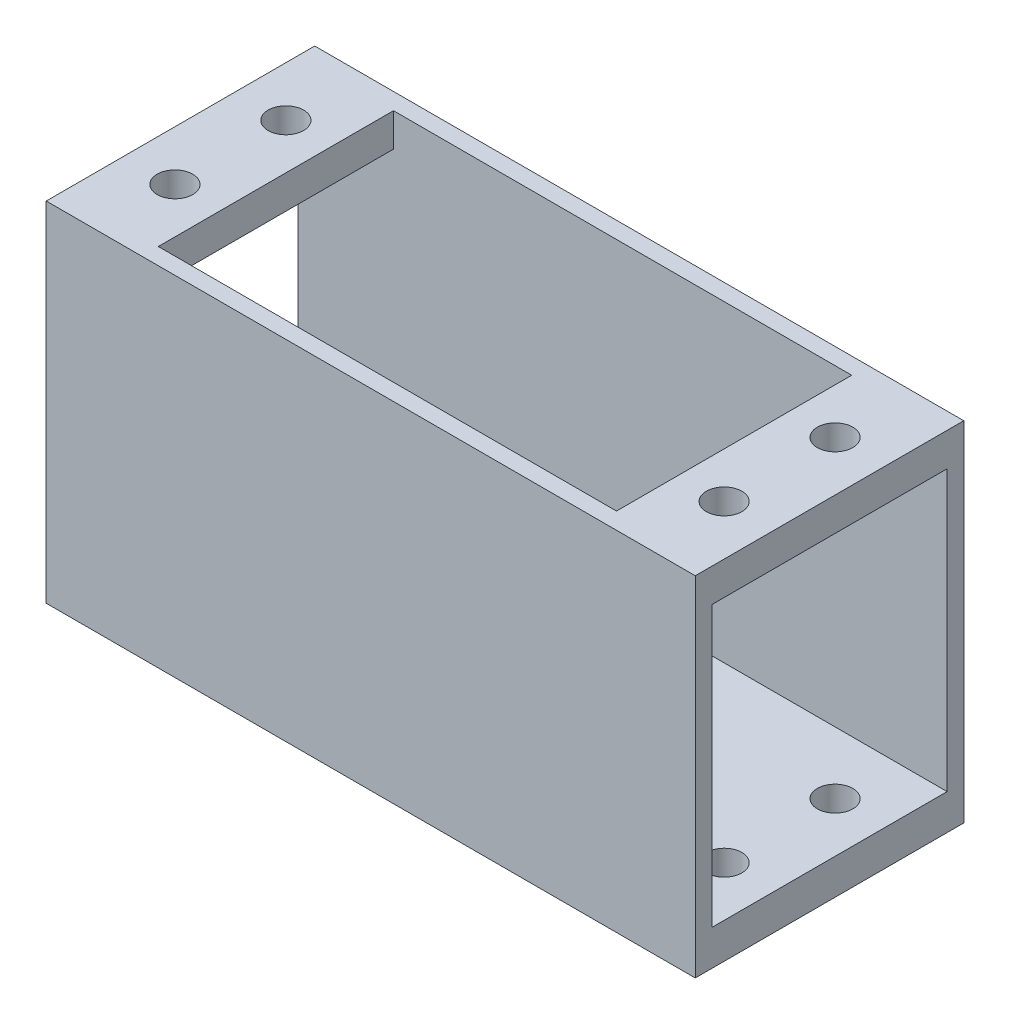
SolidWorks part; units mm, degrees
ref_plane "Front Plane" through (0, 0, 0) normal (0, 0, 1) x (1, 0, 0)
ref_plane "Top Plane" through (0, 0, 0) normal (0, 1, 0) x (1, 0, 0)
ref_plane "Right Plane" through (0, 0, 0) normal (1, 0, 0) x (0, 0, -1)
sketch "Channel Sketch" plane through (0, 0, 0) normal (1, 0, 0) x (0, 0, -1)
  line L0 (-12.1, 9.8) -> (12.1, 9.8)
  line L1 (12.1, 9.8) -> (12.1, 41.2)
  line L2 (12.1, 41.2) -> (10.6, 41.2)
  line L3 (10.6, 41.2) -> (10.6, 13)
  line L4 (10.6, 13) -> (-10.6, 13)
  line L5 (-10.6, 13) -> (-10.6, 41.2)
  line L6 (-10.6, 41.2) -> (-12.1, 41.2)
  line L7 (-12.1, 41.2) -> (-12.1, 9.8)
extrude "Channel" add sketch "Channel Sketch" along normal blind 39.35 and the other way blind 19.15
ref_axis "Stem Axis" through (0, 8.23, 0) along (0, 1, 0)
sketch "Flanges Sketch" plane through (0, 0, 0) normal (0, 0, 1) x (1, 0, 0)
  line L0 (-19.15, 38.2) -> (-10.55, 38.2)
  line L1 (-10.55, 38.2) -> (-10.55, 41.2)
  line L2 (-10.55, 41.2) -> (-19.15, 41.2)
  line L3 (-19.15, 41.2) -> (-19.15, 38.2)
  line L4 (30.75, 38.2) -> (39.35, 38.2)
  line L5 (39.35, 38.2) -> (39.35, 41.2)
  line L6 (39.35, 41.2) -> (30.75, 41.2)
  line L7 (30.75, 41.2) -> (30.75, 38.2)
extrude "Flanges" add sketch "Flanges Sketch" along normal mid plane 21.2
sketch "Servo Holes Sketch" plane through (0, 0, 0) normal (0, 1, 0) x (1, 0, 0)
  circle A0 centre (-14.65, -5) radius 1.6
  circle A1 centre (-14.65, 5) radius 1.6
  circle A2 centre (34.85, -5) radius 1.6
  circle A3 centre (34.85, 5) radius 1.6
extrude "Servo Holes" cut sketch "Servo Holes Sketch" against normal mid plane 102.4
sketch "Panel Hole Sketch" plane through (0, 0, 0) normal (0, 1, 0) x (1, 0, 0)
  circle A0 centre (0, 0) radius 7.7
extrude "Panel Hole" cut sketch "Panel Hole Sketch" against normal mid plane 28
sketch "Panel Nut Relief Sketch" plane through (0, 0, 0) normal (0, 0, 1) x (1, 0, 0)
  line L0 (0, -500) -> (0, 500) construction
  line L1 (0, 13) -> (11.5, 13)
  line L2 (11.5, 13) -> (11.5, 18)
  line L3 (11.5, 18) -> (0, 18)
  line L4 (0, 18) -> (0, 13)
revolve "Panel Nut Relief" cut sketch "Panel Nut Relief Sketch" angle 360 about L0
